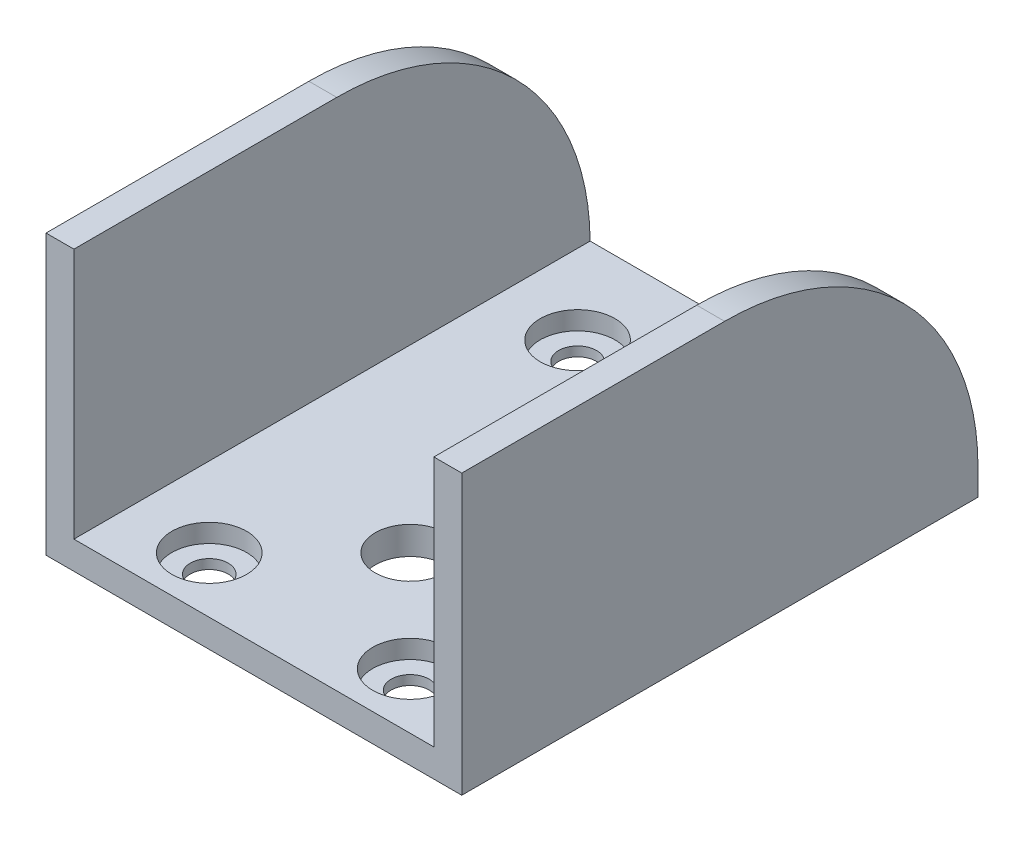
SolidWorks part; units mm, degrees
material "PBT General Purpose"
ref_plane "Front Plane" through (0, 0, 0) normal (0, 0, 1) x (1, 0, 0)
ref_plane "Top Plane" through (0, 0, 0) normal (0, 1, 0) x (1, 0, 0)
ref_plane "Right Plane" through (0, 0, 0) normal (1, 0, 0) x (0, 0, -1)
sketch "Sketch12" plane through (0, 0, 0) normal (0, 1, 0) x (1, 0, 0)
  line L1 (-16.125, -23.125) -> (16.125, -23.125)
  line L2 (-16.125, -23.125) -> (-16.125, 23.125)
  line L3 (-16.125, 23.125) -> (16.125, 23.125)
  line L4 (16.125, -23.125) -> (16.125, 23.125)
  line L5 (-16.125, -23.125) -> (16.125, 23.125) construction
  line L6 (-16.125, 23.125) -> (16.125, -23.125) construction
  point P0 (0, 0)
  dimension "D1" = 32.25
  dimension "D2" = 46.25
extrude "Boss-Extrude2" add sketch "Sketch12" along normal blind 2.5
sketch "Sketch13" plane through (0, 2.5, 0) normal (0, 1, 0) x (1, 0, 0)
  line L0 (0, 23.125) -> (0, -23.125) construction
  line L1 (-9, -18.125) -> (9, -18.125)
  line L2 (-9, -18.125) -> (-9, 14.875)
  line L3 (-9, 14.875) -> (9, 14.875)
  line L4 (9, -18.125) -> (9, 14.875)
  line L5 (-9, -18.125) -> (9, 14.875) construction
  line L6 (-9, 14.875) -> (9, -18.125) construction
  line L7 (16.125, 23.125) -> (-16.125, 23.125) construction
  line L8 (-16.125, -23.125) -> (16.125, -23.125) construction
  point P0 (0, -1.625)
  point P11 (0, -9.125)
  dimension "D1" = 33
  dimension "D2" = 18
  dimension "D3" = 5
  dimension "D4" = 14
hole_wizard "CBORE for M3 SBHCS1" positions "Sketch14" profile "Sketch15" counterbore size "M3" standard "ANSI Metric" end condition through all
sketch "Sketch14" plane through (0, 2.5, 0) normal (0, 1, 0) x (1, 0, 0)
  point P0 (-9, 14.875)
  point P3 (9, 14.875)
  point P6 (9, -18.125)
  point P9 (-9, -18.125)
sketch "Sketch15" plane through (-9, 2.5, -14.875) normal (1, 0, 0) x (0, 0, 1)
  line L0 (0, 0) -> (0, 2.5)
  line L1 (0, 2.5) -> (1.7, 2.5)
  line L3 (1.7, 2.5) -> (1.7, 1.65)
  line L4 (1.7, 1.65) -> (3.35, 1.65)
  line L5 (3.35, 1.65) -> (3.35, 0)
  line L7 (3.35, 0) -> (0, 0)
  line L11 (0, -6.35) -> (0, 107.95) construction
  dimension "Thru Hole Dia." = 3.4
  dimension "Thru Hole Depth" = 2.5
  dimension "C'Bore Dia." = 6.7
  dimension "C'Bore Depth" = 1.65
hole_wizard "Ø6.0mm Dowel Hole1" positions "Sketch18" profile "Sketch19" hole size "Ø6.0" standard "ANSI Metric" end condition through all
sketch "Sketch18" plane through (0, 2.5, 0) normal (0, 1, 0) x (1, 0, 0)
  point P0 (0, -9.125)
sketch "Sketch19" plane through (0, 2.5, 9.125) normal (1, 0, 0) x (0, 0, 1)
  line L0 (0, 0) -> (0, 2.5)
  line L1 (0, 2.5) -> (3.125, 2.5)
  line L2 (3.125, 2.5) -> (3.125, 0)
  line L5 (3.125, 0) -> (0, 0)
  line L11 (0, -6.35) -> (0, 107.95) construction
  dimension "Thru Hole Dia." = 6.25
  dimension "Thru Hole Depth" = 2.5
sketch "Sketch20" plane through (-16.125, 0, 0) normal (-1, 0, 0) x (0, 0, 1)
  line L0 (-23.125, 0) -> (23.125, 0) construction
  line L1 (23.125, 0) -> (-23.125, 0)
  line L2 (23.125, 0) -> (23.125, 25)
  line L3 (23.125, 25) -> (-23.125, 25)
  line L4 (-23.125, 0) -> (-23.125, 25)
  line L5 (-23.125, 2.5) -> (-23.125, 0) construction
  line L6 (23.125, 2.5) -> (23.125, 0) construction
  dimension "D1" = 25
ref_plane "Plane1" through (0, 0, 0) normal (-1, 0, 0) x (0, 0, 1)
extrude "Boss-Extrude3" add sketch "Sketch20" along normal blind 2.5 contours L4 L3 L2 L1
mirror "Mirror1" about plane through (0, 0, 0) normal (-1, 0, 0) of "Boss-Extrude3"
fillet "Fillet1" radius 22.7 1 edges at (-17.375, 25, -23.125)
